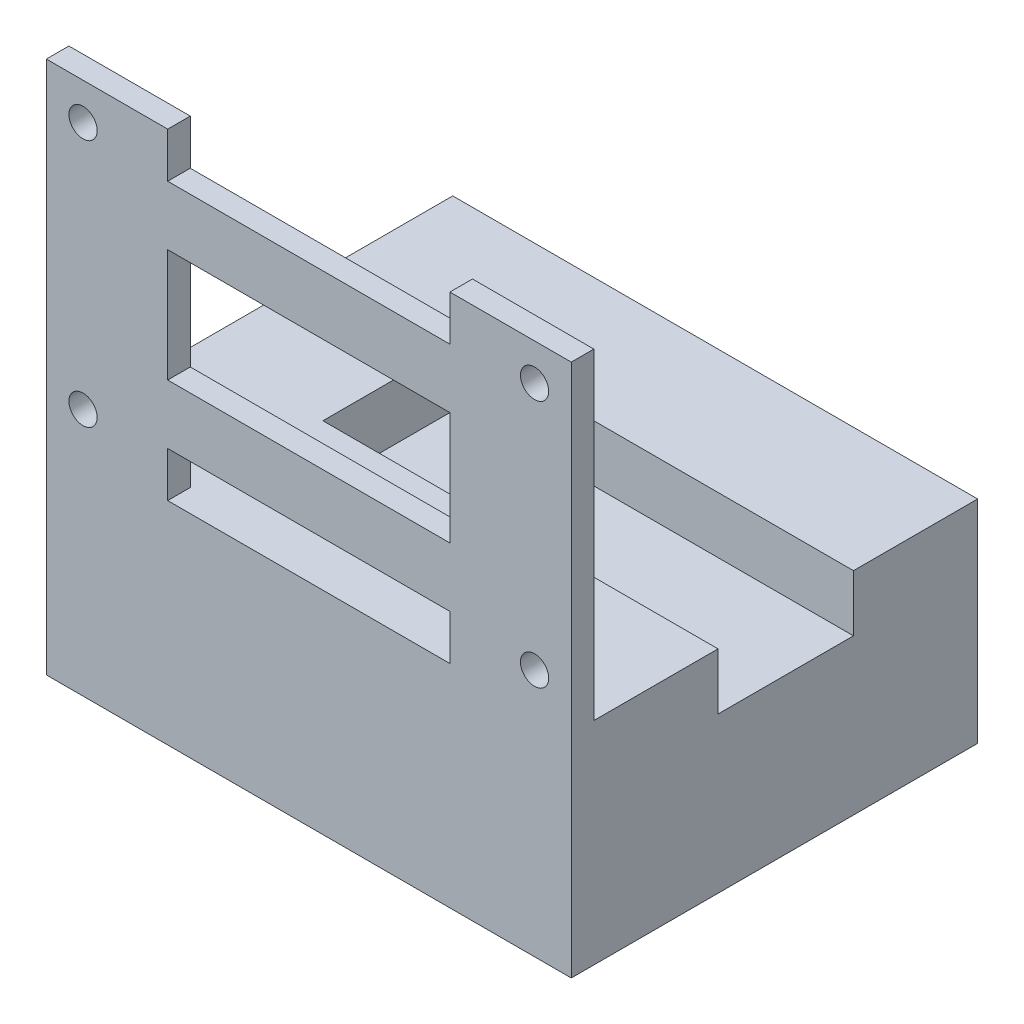
SolidWorks part; units mm, degrees
ref_plane "Front Plane" through (0, 0, 0) normal (0, 0, 1) x (1, 0, 0)
ref_plane "Top Plane" through (0, 0, 0) normal (0, 1, 0) x (1, 0, 0)
ref_plane "Right Plane" through (0, 0, 0) normal (1, 0, 0) x (0, 0, -1)
sketch "Sketch1" plane through (0, 0, 0) normal (0, 1, 0) x (1, 0, 0)
  line L1 (-23.25, -17) -> (23.25, -17)
  line L2 (-23.25, -17) -> (-23.25, 17)
  line L3 (-23.25, 17) -> (23.25, 17)
  line L4 (23.25, -17) -> (23.25, 17)
  line L5 (-23.25, -17) -> (23.25, 17) construction
  line L6 (-23.25, 17) -> (23.25, -17) construction
  point P0 (0, 0)
  dimension "D1" = 46.5
  dimension "D2" = 34
extrude "Boss-Extrude1" add sketch "Sketch1" along normal blind 13.75
sketch "Sketch2" plane through (0, 0, 17) normal (0, 0, 1) x (1, 0, 0)
  line L1 (-23.25, 0) -> (23.25, 0)
  line L2 (-23.25, 0) -> (-23.25, 42.25)
  line L3 (-23.25, 42.25) -> (23.25, 42.25)
  line L4 (23.25, 0) -> (23.25, 42.25)
  dimension "D1" = 46.5
  dimension "D2" = 42.25
extrude "Boss-Extrude2" add sketch "Sketch2" along normal blind 2
sketch "Sketch3" plane through (0, 0, 19) normal (0, 0, 1) x (1, 0, 0)
  line L0 (-23.25, 28) -> (23.25, 28) construction
  line L1 (-12.5, 33) -> (12.5, 33)
  line L2 (-12.5, 33) -> (-12.5, 23)
  line L3 (-12.5, 23) -> (12.5, 23)
  line L4 (12.5, 33) -> (12.5, 23)
  line L5 (23.25, 0) -> (23.25, 42.25) construction
  line L6 (23.25, 42.25) -> (-23.25, 42.25) construction
  line L7 (-23.25, 42.25) -> (-23.25, 0) construction
  circle A0 centre (-20, 39) radius 1.25
  circle A2 centre (20, 39) radius 1.25
  circle A4 centre (20, 17) radius 1.25
  circle A5 centre (-20, 17) radius 1.25
  dimension "D1" = 2.5
  dimension "D11" = 2.5
  dimension "D2" = 10
  dimension "D3" = 25
  dimension "D4" = 5
  dimension "D5" = 10.75
  dimension "D6" = 14.25
  dimension "D7" = 3.25
  dimension "D8" = 3.25
  dimension "D9" = 3.25
  dimension "D10" = 3.25
extrude "Cut-Extrude1" cut sketch "Sketch3" against normal up to next
sketch "Sketch4" plane through (0, 13.75, 0) normal (0, 1, 0) x (1, 0, 0)
  line L0 (23.25, -17) -> (23.25, 17) construction
  line L1 (23.25, 6) -> (-11.75, 6)
  line L2 (23.25, 6) -> (23.25, -6)
  line L3 (23.25, -6) -> (-11.75, -6)
  line L4 (-11.75, 6) -> (-11.75, -6)
  line L5 (23.25, 17) -> (-23.25, 17) construction
  dimension "D1" = 35
  dimension "D2" = 12
  dimension "D3" = 11
extrude "Cut-Extrude2" cut sketch "Sketch4" against normal blind 5
sketch "Sketch6" plane through (0, 0, 0) normal (0, -1, 0) x (1, 0, 0)
  line L0 (16.25, -10) -> (16.25, 12)
  line L1 (23.25, -17) -> (-23.25, -17)
  line L2 (23.25, -17) -> (23.25, 19)
  line L3 (23.25, 19) -> (-23.25, 19)
  line L4 (-23.25, -17) -> (-23.25, 19)
  line L5 (16.25, 12) -> (-16.25, 12)
  line L6 (-16.25, -10) -> (-16.25, 12)
  line L7 (16.25, -10) -> (-16.25, -10)
  circle A0 centre (16.25, -10) radius 2
  circle A1 centre (16.25, 12) radius 2
  circle A2 centre (-16.25, -10) radius 2
  circle A3 centre (-16.25, 12) radius 2
  line M9 (23.25, -17) -> (23.25, 19)
  line M10 (23.25, 19) -> (-23.25, 19)
  line M11 (-23.25, 19) -> (-23.25, -17)
  line M12 (-23.25, -17) -> (23.25, -17)
  dimension "D2" = 4
  dimension "D3" = 4
  dimension "D4" = 4
  dimension "D5" = 4
  dimension "D1" = 7
extrude "Boss-Extrude3" add sketch "Sketch6" along normal blind 5 contours A3 L6 A2 L7 A0 L0 A1 L5 | A3 L5 A1 L0 A0 L7 A2 L6 M12 M9 M10 M11 region at (0, 0, 1) region at (0, 0, -16.4119)
sketch "Sketch7" plane through (0, 0, 17) normal (0, 0, -1) x (-1, 0, 0)
  line L0 (23.25, 13.75) -> (-23.25, 13.75) construction
  line L1 (-12.5, 13.75) -> (12.5, 13.75)
  line L2 (-12.5, 13.75) -> (-12.5, 17.75)
  line L3 (-12.5, 17.75) -> (12.5, 17.75)
  line L4 (12.5, 13.75) -> (12.5, 17.75)
  line L5 (-23.25, 42.25) -> (23.25, 42.25) construction
  line L6 (-12.5, 42.25) -> (12.5, 42.25)
  line L7 (-12.5, 42.25) -> (-12.5, 38.25)
  line L8 (-12.5, 38.25) -> (12.5, 38.25)
  line L9 (12.5, 42.25) -> (12.5, 38.25)
  dimension "D1" = 4
  dimension "D2" = 4
extrude "Cut-Extrude3" cut sketch "Sketch7" against normal blind 10
